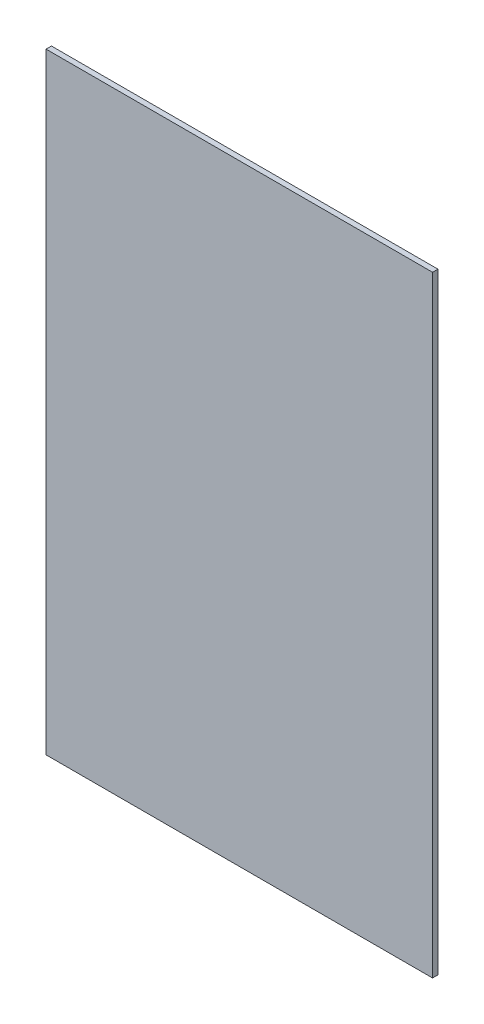
SolidWorks part; units mm, degrees
ref_plane "Front Plane" through (0, 0, 0) normal (0, 0, 1) x (1, 0, 0)
ref_plane "Top Plane" through (0, 0, 0) normal (0, 1, 0) x (1, 0, 0)
ref_plane "Right Plane" through (0, 0, 0) normal (1, 0, 0) x (0, 0, -1)
sketch "Sketch1" plane through (0, 0, -122.5) normal (0, 0, -1) x (-1, 0, 0)
  line L0 (107.5, 330) -> (-107.5, 330) construction
  line L1 (-107.5, 330) -> (107.5, 330)
  line L2 (-107.5, 330) -> (-107.5, -10)
  line L3 (-107.5, -10) -> (107.5, -10)
  line L4 (107.5, 330) -> (107.5, -10)
  line L5 (-107.5, 10) -> (-107.5, 310) construction
  line L6 (107.5, 10) -> (107.5, 310) construction
  line L7 (-87.5, -10) -> (87.5, -10) construction
base flange "Base-Flange1" sketch "Sketch1" thickness 3 reverse thickness direction yes parameters "D1"=3
sketch "Bend-Lines1" [suppressed] plane through (0, 0, 0) normal (0, 1, 0) x (1, 0, 0)
sketch "Bounding-Box1" [suppressed] plane through (0, 0, 0) normal (0, 1, 0) x (1, 0, 0)
sheet metal parameters "Sheet-Metal1" thickness 3 parameters "D1"=3
flat pattern "Flat-Pattern1" [suppressed]
sketch "Bend-Lines2" plane through (0, 0, 0) normal (0, 1, 0) x (1, 0, 0)
sketch3d "Bounding-Box2" [suppressed]
  line L0 (-107.5, 330, 0) -> (-107.5, -10, 0) construction
  line L1 (107.5, 330, 0) -> (107.5, -10, 0) construction
  line L2 (-107.5, 330, 0) -> (107.5, 330, 0) construction
  line L3 (-107.5, -10, 0) -> (107.5, -10, 0) construction
